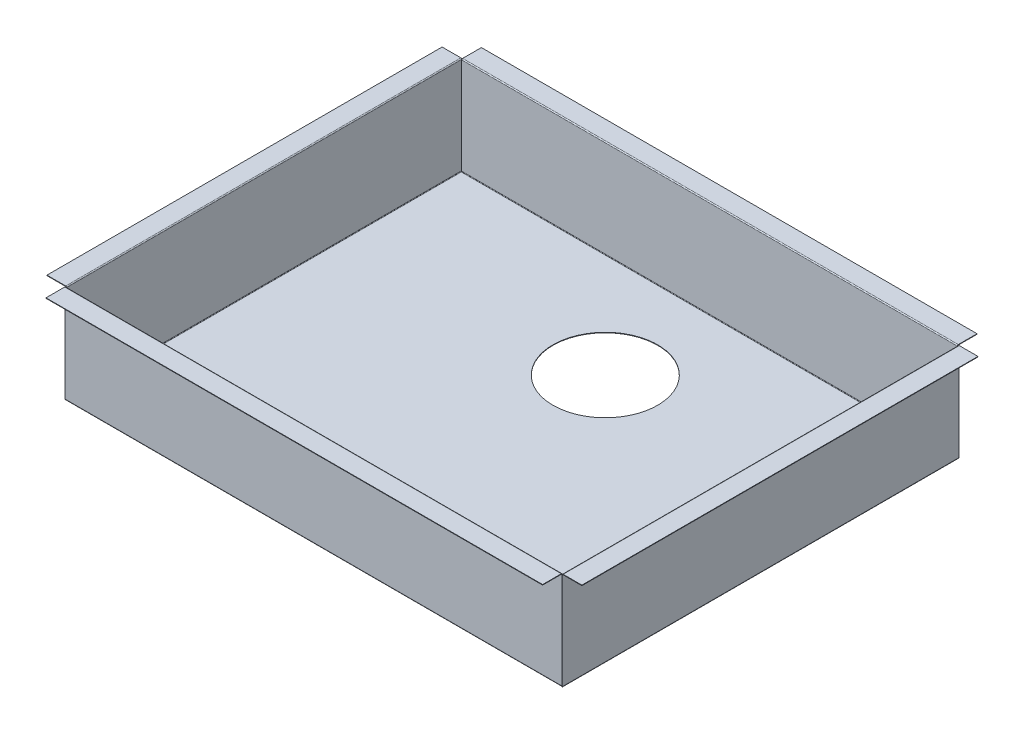
SolidWorks part; units mm, degrees
note: The reader was unsure of these and kept them because the rebuilt part matched: flange length of "Edge-Flange1", "Edge-Flange2", "Edge-Flange3", "Edge-Flange4", "Edge-Flange5", "Edge-Flange6", "Edge-Flange7", "Edge-Flange8".
ref_plane "Front Plane" through (0, 0, 0) normal (0, 0, 1) x (1, 0, 0)
ref_plane "Top Plane" through (0, 0, 0) normal (0, 1, 0) x (1, 0, 0)
ref_plane "Right Plane" through (0, 0, 0) normal (1, 0, 0) x (0, 0, -1)
sketch "Sketch1" plane through (0, 0, 0) normal (0, 1, 0) x (1, 0, 0)
  line L1 (-380, -302.5) -> (380, -302.5)
  line L2 (-380, -302.5) -> (-380, 302.5)
  line L3 (-380, 302.5) -> (380, 302.5)
  line L4 (380, -302.5) -> (380, 302.5)
  line L5 (-380, -302.5) -> (380, 302.5) construction
  line L6 (-380, 302.5) -> (380, -302.5) construction
  circle A0 centre (0, 142.5) radius 80
  point P0 (0, 0)
  dimension "D3" = 160
  dimension "D4" = 380
  dimension "D5" = 445
  dimension "D1" = 760
  dimension "D2" = 605
base flange "Base-Flange1" sketch "Sketch1" thickness 0.7366 reverse thickness direction no parameters "D1"=0.7366
edge flange "Edge-Flange1" sketch "Sketch8" flange angle 90 flange length 150 flange position material inside bend radius 0.7366 thickness 0.7366 relief rectangular parameters "D6"=10
sketch "Sketch8" plane through (380, 0, 0) normal (1, 0, 0) x (0, 0, -1)
  line L0 (-302.5, 0) -> (302.5, 0) construction
  line L1 (-302.5, 0) -> (302.5, 0)
  line L2 (-302.5, 0) -> (-302.5, 149.2634)
  line L3 (-302.5, 149.2634) -> (302.5, 149.2634)
  line L4 (302.5, 149.2634) -> (302.5, 0)
bend "EdgeBend1" bend radius 0.7366 bend angle 90 parameters "D5"=1
edge flange "Edge-Flange2" sketch "Sketch11" flange angle 90 flange length 150 flange position material inside bend radius 0.7366 thickness 0.7366 relief none parameters "D6"=10
sketch "Sketch11" plane through (0, 0, 302.5) normal (0, 0, 1) x (1, 0, 0)
  line L0 (-380, 0) -> (378.5268, 0) construction
  line L1 (-380, 0) -> (378.5268, 0)
  line L2 (-380, 0) -> (-380, 149.2634)
  line L3 (-380, 149.2634) -> (378.5268, 149.2634)
  line L4 (378.5268, 149.2634) -> (378.5268, 0)
bend "EdgeBend2" bend radius 0.7366 bend angle 90 parameters "D5"=2
edge flange "Edge-Flange3" sketch "Sketch14" flange angle 90 flange length 150 flange position material inside bend radius 0.7366 thickness 0.7366 relief none parameters "D6"=10
sketch "Sketch14" plane through (-380, 0, 0) normal (-1, 0, 0) x (0, 0, 1)
  line L0 (-302.5, 0) -> (301.0268, 0) construction
  line L1 (-302.5, 0) -> (301.0268, 0)
  line L2 (-302.5, 0) -> (-302.5, 149.2634)
  line L3 (-302.5, 149.2634) -> (301.0268, 149.2634)
  line L4 (301.0268, 149.2634) -> (301.0268, 0)
bend "EdgeBend3" bend radius 0.7366 bend angle 90 parameters "D5"=3
edge flange "Edge-Flange4" sketch "Sketch17" flange angle 90 flange length 150 flange position material inside bend radius 0.7366 thickness 0.7366 relief none parameters "D6"=10
sketch "Sketch17" plane through (0, 0, -302.5) normal (0, 0, -1) x (-1, 0, 0)
  line L0 (-378.5268, 0) -> (378.5268, 0) construction
  line L1 (-378.5268, 0) -> (378.5268, 0)
  line L2 (-378.5268, 0) -> (-378.5268, 149.2634)
  line L3 (-378.5268, 149.2634) -> (378.5268, 149.2634)
  line L4 (378.5268, 149.2634) -> (378.5268, 0)
bend "EdgeBend4" bend radius 0.7366 bend angle 90 parameters "D5"=4
edge flange "Edge-Flange5" sketch "Sketch20" flange angle 90 flange length 30 flange position material inside bend radius 0.7366 thickness 0.7366 relief rectangular parameters "D6"=10
sketch "Sketch20" plane through (0, 149.2634, 302.5) normal (0, 1, 0) x (-1, 0, 0)
  line L0 (-378.5268, 0) -> (380, 0) construction
  line L1 (-378.5268, 0) -> (380, 0)
  line L2 (-378.5268, 0) -> (-378.5268, 29.2634)
  line L3 (-378.5268, 29.2634) -> (380, 29.2634)
  line L4 (380, 29.2634) -> (380, 0)
bend "EdgeBend5" bend radius 0.7366 bend angle 90 parameters "D5"=5
edge flange "Edge-Flange6" sketch "Sketch23" flange angle 90 flange length 30 flange position material inside bend radius 0.7366 thickness 0.7366 relief rectangular parameters "D6"=10
sketch "Sketch23" plane through (-380, 149.2634, 0) normal (0, 1, 0) x (0, 0, -1)
  line L0 (-301.0268, 0) -> (302.5, 0) construction
  line L1 (-301.0268, 0) -> (302.5, 0)
  line L2 (-301.0268, 0) -> (-301.0268, 29.2634)
  line L3 (-301.0268, 29.2634) -> (302.5, 29.2634)
  line L4 (302.5, 29.2634) -> (302.5, 0)
bend "EdgeBend6" bend radius 0.7366 bend angle 90 parameters "D5"=6
edge flange "Edge-Flange7" sketch "Sketch26" flange angle 90 flange length 30 flange position material inside bend radius 0.7366 thickness 0.7366 relief rectangular parameters "D6"=10
sketch "Sketch26" plane through (0, 149.2634, -302.5) normal (0, 1, 0) x (1, 0, 0)
  line L0 (-378.5268, 0) -> (378.5268, 0) construction
  line L1 (-378.5268, 0) -> (378.5268, 0)
  line L2 (-378.5268, 0) -> (-378.5268, 29.2634)
  line L3 (-378.5268, 29.2634) -> (378.5268, 29.2634)
  line L4 (378.5268, 29.2634) -> (378.5268, 0)
bend "EdgeBend7" bend radius 0.7366 bend angle 90 parameters "D5"=7
edge flange "Edge-Flange8" sketch "Sketch29" flange angle 90 flange length 30 flange position material inside bend radius 0.7366 thickness 0.7366 relief rectangular parameters "D6"=10
sketch "Sketch29" plane through (380, 149.2634, 0) normal (0, 1, 0) x (0, 0, 1)
  line L0 (-302.5, 0) -> (302.5, 0) construction
  line L1 (-302.5, 0) -> (302.5, 0)
  line L2 (-302.5, 0) -> (-302.5, 29.2634)
  line L3 (-302.5, 29.2634) -> (302.5, 29.2634)
  line L4 (302.5, 29.2634) -> (302.5, 0)
bend "EdgeBend8" bend radius 0.7366 bend angle 90 parameters "D5"=8
sketch "Bend-Lines1" [suppressed] plane through (0, 0, 0) normal (0, 1, 0) x (1, 0, 0)
sketch "Bounding-Box1" [suppressed] plane through (0, 0, 0) normal (0, 1, 0) x (1, 0, 0)
sheet metal parameters "Sheet-Metal1" thickness 0.7366 parameters "D1"=0.7366
flat pattern "Flat-Pattern1" [suppressed]
sketch "Bend-Lines2" plane through (0, 0, 0) normal (0, 1, 0) x (1, 0, 0)
sketch3d "Bounding-Box2" [suppressed]
  line L0 (-380, 302.5, 0) -> (380, 302.5, 0) construction
  line L1 (-380, -302.5, 0) -> (380, -302.5, 0) construction
  line L2 (-380, 302.5, 0) -> (-380, -302.5, 0) construction
  line L3 (380, 302.5, 0) -> (380, -302.5, 0) construction
sheet metal parameters "Sheet-Metal2" thickness 0.7366 parameters "D1"=0.7366
flat pattern "Flat-Pattern1"
sketch "Bend-Lines2" plane through (0, 0, 0) normal (0, 1, 0) x (1, 0, 0)
  line L0 (379.3946, -302.5) -> (379.3946, 302.5) construction
  line L1 (379.3946, -302.5) -> (379.3946, 302.5) construction
sketch3d "Bounding-Box2" [suppressed]
  line L0 (528.7892, 302.5, 0) -> (-380, 302.5, 0) construction
  line L1 (528.7892, -302.5, 0) -> (-380, -302.5, 0) construction
  line L2 (528.7892, 302.5, 0) -> (528.7892, -302.5, 0) construction
  line L3 (-380, 302.5, 0) -> (-380, -302.5, 0) construction
bend of the flat pattern "Flatten-<EdgeBend1>1"
sheet metal parameters "Sheet-Metal3" thickness 0.7366 parameters "D1"=0.7366
flat pattern "Flat-Pattern1"
sketch "Bend-Lines2" plane through (0, 0, 0) normal (0, 1, 0) x (1, 0, 0)
  line L0 (379.3946, -302.5) -> (379.3946, 302.5) construction
  line L1 (379.3946, -302.5) -> (379.3946, 302.5) construction
  line L2 (-380, -301.8946) -> (378.5268, -301.8946) construction
  line L3 (-380, -301.8946) -> (378.5268, -301.8946) construction
sketch3d "Bounding-Box2" [suppressed]
  line L0 (528.7892, 302.5, 0) -> (-380, 302.5, 0) construction
  line L1 (528.7892, -451.2892, 0) -> (-380, -451.2892, 0) construction
  line L2 (528.7892, 302.5, 0) -> (528.7892, -451.2892, 0) construction
  line L3 (-380, 302.5, 0) -> (-380, -451.2892, 0) construction
bend of the flat pattern "Flatten-<EdgeBend1>1"
bend of the flat pattern "Flatten-<EdgeBend2>1"
sheet metal parameters "Sheet-Metal4" thickness 0.7366 parameters "D1"=0.7366
flat pattern "Flat-Pattern1"
sketch "Bend-Lines2" plane through (0, 0, 0) normal (0, 1, 0) x (1, 0, 0)
  line L0 (379.3946, -302.5) -> (379.3946, 302.5) construction
  line L1 (379.3946, -302.5) -> (379.3946, 302.5) construction
  line L2 (-380, -301.8946) -> (378.5268, -301.8946) construction
  line L3 (-380, -301.8946) -> (378.5268, -301.8946) construction
  line L4 (-379.3946, 302.5) -> (-379.3946, -301.0268) construction
  line L5 (-379.3946, 302.5) -> (-379.3946, -301.0268) construction
sketch3d "Bounding-Box2" [suppressed]
  line L0 (528.7892, 302.5, 0) -> (-528.7892, 302.5, 0) construction
  line L1 (528.7892, -451.2892, 0) -> (-528.7892, -451.2892, 0) construction
  line L2 (528.7892, 302.5, 0) -> (528.7892, -451.2892, 0) construction
  line L3 (-528.7892, 302.5, 0) -> (-528.7892, -451.2892, 0) construction
bend of the flat pattern "Flatten-<EdgeBend1>1"
bend of the flat pattern "Flatten-<EdgeBend2>1"
bend of the flat pattern "Flatten-<EdgeBend3>1"
sheet metal parameters "Sheet-Metal5" thickness 0.7366 parameters "D1"=0.7366
flat pattern "Flat-Pattern1"
sketch "Bend-Lines2" plane through (0, 0, 0) normal (0, 1, 0) x (1, 0, 0)
  line L0 (379.3946, -302.5) -> (379.3946, 302.5) construction
  line L1 (379.3946, -302.5) -> (379.3946, 302.5) construction
  line L2 (-380, -301.8946) -> (378.5268, -301.8946) construction
  line L3 (-380, -301.8946) -> (378.5268, -301.8946) construction
  line L4 (-379.3946, 302.5) -> (-379.3946, -301.0268) construction
  line L5 (-379.3946, 302.5) -> (-379.3946, -301.0268) construction
  line L6 (378.5268, 301.8946) -> (-378.5268, 301.8946) construction
  line L7 (378.5268, 301.8946) -> (-378.5268, 301.8946) construction
sketch3d "Bounding-Box2" [suppressed]
  line L0 (528.7892, 451.2892, 0) -> (-528.7892, 451.2892, 0) construction
  line L1 (528.7892, -451.2892, 0) -> (-528.7892, -451.2892, 0) construction
  line L2 (528.7892, 451.2892, 0) -> (528.7892, -451.2892, 0) construction
  line L3 (-528.7892, 451.2892, 0) -> (-528.7892, -451.2892, 0) construction
bend of the flat pattern "Flatten-<EdgeBend1>1"
bend of the flat pattern "Flatten-<EdgeBend2>1"
bend of the flat pattern "Flatten-<EdgeBend3>1"
bend of the flat pattern "Flatten-<EdgeBend4>1"
sheet metal parameters "Sheet-Metal6" thickness 0.7366 parameters "D1"=0.7366
flat pattern "Flat-Pattern1"
sketch "Bend-Lines2" plane through (0, 0, 0) normal (0, 1, 0) x (1, 0, 0)
  line L0 (379.3946, -302.5) -> (379.3946, 302.5) construction
  line L1 (379.3946, -302.5) -> (379.3946, 302.5) construction
  line L2 (-380, -301.8946) -> (378.5268, -301.8946) construction
  line L3 (-380, -301.8946) -> (378.5268, -301.8946) construction
  line L4 (-379.3946, 302.5) -> (-379.3946, -301.0268) construction
  line L5 (-379.3946, 302.5) -> (-379.3946, -301.0268) construction
  line L6 (378.5268, 301.8946) -> (-378.5268, 301.8946) construction
  line L7 (378.5268, 301.8946) -> (-378.5268, 301.8946) construction
  line L8 (-380, -450.6838) -> (378.5268, -450.6838) construction
  line L9 (-380, -450.6838) -> (378.5268, -450.6838) construction
sketch3d "Bounding-Box2" [suppressed]
  line L0 (528.7892, 451.2892, 0) -> (-528.7892, 451.2892, 0) construction
  line L1 (528.7892, -480.0783, 0) -> (-528.7892, -480.0783, 0) construction
  line L2 (528.7892, 451.2892, 0) -> (528.7892, -480.0783, 0) construction
  line L3 (-528.7892, 451.2892, 0) -> (-528.7892, -480.0783, 0) construction
bend of the flat pattern "Flatten-<EdgeBend1>1"
bend of the flat pattern "Flatten-<EdgeBend2>1"
bend of the flat pattern "Flatten-<EdgeBend3>1"
bend of the flat pattern "Flatten-<EdgeBend4>1"
bend of the flat pattern "Flatten-<EdgeBend5>1"
sheet metal parameters "Sheet-Metal7" thickness 0.7366 parameters "D1"=0.7366
flat pattern "Flat-Pattern1"
sketch "Bend-Lines2" plane through (0, 0, 0) normal (0, 1, 0) x (1, 0, 0)
  line L0 (379.3946, -302.5) -> (379.3946, 302.5) construction
  line L1 (379.3946, -302.5) -> (379.3946, 302.5) construction
  line L2 (-380, -301.8946) -> (378.5268, -301.8946) construction
  line L3 (-380, -301.8946) -> (378.5268, -301.8946) construction
  line L4 (-379.3946, 302.5) -> (-379.3946, -301.0268) construction
  line L5 (-379.3946, 302.5) -> (-379.3946, -301.0268) construction
  line L6 (378.5268, 301.8946) -> (-378.5268, 301.8946) construction
  line L7 (378.5268, 301.8946) -> (-378.5268, 301.8946) construction
  line L8 (-380, -450.6838) -> (378.5268, -450.6838) construction
  line L9 (-380, -450.6838) -> (378.5268, -450.6838) construction
  line L10 (-528.1838, 302.5) -> (-528.1838, -301.0268) construction
  line L11 (-528.1838, 302.5) -> (-528.1838, -301.0268) construction
sketch3d "Bounding-Box2" [suppressed]
  line L0 (528.7892, 451.2892, 0) -> (-557.5783, 451.2892, 0) construction
  line L1 (528.7892, -480.0783, 0) -> (-557.5783, -480.0783, 0) construction
  line L2 (528.7892, 451.2892, 0) -> (528.7892, -480.0783, 0) construction
  line L3 (-557.5783, 451.2892, 0) -> (-557.5783, -480.0783, 0) construction
bend of the flat pattern "Flatten-<EdgeBend1>1"
bend of the flat pattern "Flatten-<EdgeBend2>1"
bend of the flat pattern "Flatten-<EdgeBend3>1"
bend of the flat pattern "Flatten-<EdgeBend4>1"
bend of the flat pattern "Flatten-<EdgeBend5>1"
bend of the flat pattern "Flatten-<EdgeBend6>1"
sheet metal parameters "Sheet-Metal8" thickness 0.7366 parameters "D1"=0.7366
flat pattern "Flat-Pattern1"
sketch "Bend-Lines2" plane through (0, 0, 0) normal (0, 1, 0) x (1, 0, 0)
  line L0 (379.3946, -302.5) -> (379.3946, 302.5) construction
  line L1 (379.3946, -302.5) -> (379.3946, 302.5) construction
  line L2 (-380, -301.8946) -> (378.5268, -301.8946) construction
  line L3 (-380, -301.8946) -> (378.5268, -301.8946) construction
  line L4 (-379.3946, 302.5) -> (-379.3946, -301.0268) construction
  line L5 (-379.3946, 302.5) -> (-379.3946, -301.0268) construction
  line L6 (378.5268, 301.8946) -> (-378.5268, 301.8946) construction
  line L7 (378.5268, 301.8946) -> (-378.5268, 301.8946) construction
  line L8 (-380, -450.6838) -> (378.5268, -450.6838) construction
  line L9 (-380, -450.6838) -> (378.5268, -450.6838) construction
  line L10 (-528.1838, 302.5) -> (-528.1838, -301.0268) construction
  line L11 (-528.1838, 302.5) -> (-528.1838, -301.0268) construction
  line L12 (378.5268, 450.6838) -> (-378.5268, 450.6838) construction
  line L13 (378.5268, 450.6838) -> (-378.5268, 450.6838) construction
sketch3d "Bounding-Box2" [suppressed]
  line L0 (528.7892, 480.0783, 0) -> (-557.5783, 480.0783, 0) construction
  line L1 (528.7892, -480.0783, 0) -> (-557.5783, -480.0783, 0) construction
  line L2 (528.7892, 480.0783, 0) -> (528.7892, -480.0783, 0) construction
  line L3 (-557.5783, 480.0783, 0) -> (-557.5783, -480.0783, 0) construction
bend of the flat pattern "Flatten-<EdgeBend1>1"
bend of the flat pattern "Flatten-<EdgeBend2>1"
bend of the flat pattern "Flatten-<EdgeBend3>1"
bend of the flat pattern "Flatten-<EdgeBend4>1"
bend of the flat pattern "Flatten-<EdgeBend5>1"
bend of the flat pattern "Flatten-<EdgeBend6>1"
bend of the flat pattern "Flatten-<EdgeBend7>1"
sheet metal parameters "Sheet-Metal9" thickness 0.7366 parameters "D1"=0.7366
flat pattern "Flat-Pattern1"
sketch "Bend-Lines2" plane through (0, 0, 0) normal (0, 1, 0) x (1, 0, 0)
  line L0 (379.3946, -302.5) -> (379.3946, 302.5) construction
  line L1 (379.3946, -302.5) -> (379.3946, 302.5) construction
  line L2 (-380, -301.8946) -> (378.5268, -301.8946) construction
  line L3 (-380, -301.8946) -> (378.5268, -301.8946) construction
  line L4 (-379.3946, 302.5) -> (-379.3946, -301.0268) construction
  line L5 (-379.3946, 302.5) -> (-379.3946, -301.0268) construction
  line L6 (378.5268, 301.8946) -> (-378.5268, 301.8946) construction
  line L7 (378.5268, 301.8946) -> (-378.5268, 301.8946) construction
  line L8 (-380, -450.6838) -> (378.5268, -450.6838) construction
  line L9 (-380, -450.6838) -> (378.5268, -450.6838) construction
  line L10 (-528.1838, 302.5) -> (-528.1838, -301.0268) construction
  line L11 (-528.1838, 302.5) -> (-528.1838, -301.0268) construction
  line L12 (378.5268, 450.6838) -> (-378.5268, 450.6838) construction
  line L13 (378.5268, 450.6838) -> (-378.5268, 450.6838) construction
  line L14 (528.1838, -302.5) -> (528.1838, 302.5) construction
  line L15 (528.1838, -302.5) -> (528.1838, 302.5) construction
sketch3d "Bounding-Box2" [suppressed]
  line L0 (557.5783, 480.0783, 0) -> (-557.5783, 480.0783, 0) construction
  line L1 (557.5783, -480.0783, 0) -> (-557.5783, -480.0783, 0) construction
  line L2 (557.5783, 480.0783, 0) -> (557.5783, -480.0783, 0) construction
  line L3 (-557.5783, 480.0783, 0) -> (-557.5783, -480.0783, 0) construction
bend of the flat pattern "Flatten-<EdgeBend1>1"
bend of the flat pattern "Flatten-<EdgeBend2>1"
bend of the flat pattern "Flatten-<EdgeBend3>1"
bend of the flat pattern "Flatten-<EdgeBend4>1"
bend of the flat pattern "Flatten-<EdgeBend5>1"
bend of the flat pattern "Flatten-<EdgeBend6>1"
bend of the flat pattern "Flatten-<EdgeBend7>1"
bend of the flat pattern "Flatten-<EdgeBend8>1"
